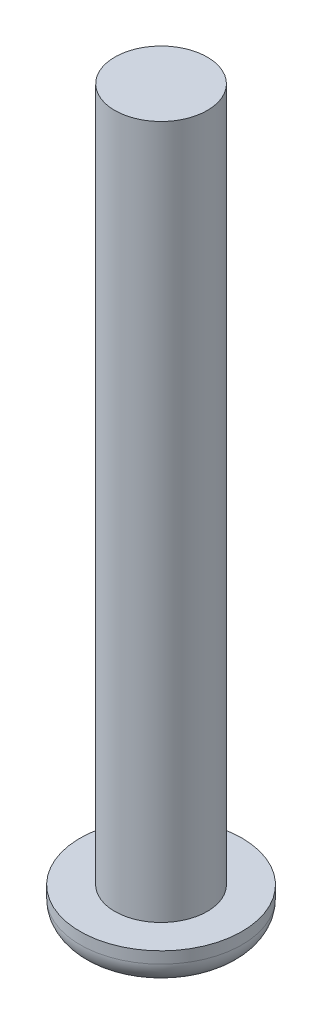
SolidWorks part; units mm, degrees
ref_plane "Front Plane" through (0, 0, 0) normal (0, 0, 1) x (1, 0, 0)
ref_plane "Top Plane" through (0, 0, 0) normal (0, 1, 0) x (1, 0, 0)
ref_plane "Right Plane" through (0, 0, 0) normal (1, 0, 0) x (0, 0, -1)
sketch "Sketch1" plane through (0, 0, 0) normal (0, 1, 0) x (1, 0, 0)
  circle A0 centre (0, 0) radius 4
  dimension "D1" = 8
extrude "Boss-Extrude1" add sketch "Sketch1" along normal blind 60 contours A0
sketch "Sketch2" plane through (0, 0, 0) normal (0, -1, 0) x (1, 0, 0)
  circle A0 centre (0, 0) radius 7
  circle A1 centre (0, 0) radius 4 construction
  circle A2 centre (0, 0) radius 4 construction
  dimension "D1" = 3
extrude "Boss-Extrude2" add sketch "Sketch2" along normal blind 3
fillet "Fillet1" radius 2 1 edges at (0, -3, -7)
sketch "Sketch3" plane through (0, -3, 0) normal (0, -1, 0) x (1, 0, 0)
  line L0 (0.375, 0.375) -> (1.5, 0.375)
  line L1 (-0.375, -1.5) -> (0.375, -1.5)
  line L2 (-0.375, -1.5) -> (-0.375, -0.375)
  line L3 (-0.375, 1.5) -> (0.375, 1.5)
  line L4 (0.375, -1.5) -> (0.375, -0.375)
  line L7 (-1.5, -0.375) -> (-0.375, -0.375)
  line L8 (-1.5, -0.375) -> (-1.5, 0.375)
  line L9 (-1.5, 0.375) -> (-0.375, 0.375)
  line L10 (1.5, -0.375) -> (1.5, 0.375)
  line L15 (0.375, 0.375) -> (0.375, 1.5)
  line L16 (0.375, -0.375) -> (1.5, -0.375)
  line L17 (-0.375, 0.375) -> (-0.375, 1.5)
  point P0 (0, 0)
  point P6 (0, 0)
  dimension "D1" = 3
  dimension "D2" = 0.75
extrude "Cut-Extrude1" cut sketch "Sketch3" against normal blind 1 draft 15
sketch "Sketch5" [suppressed] plane through (0, 0, 0) normal (0, 0, 1) x (1, 0, 0)
  line L0 (-3.5, -2) -> (3.5, -2) construction
  line L3 (0, 0) -> (0, 24) construction
  point P6 (0, 11)
  dimension "D1" = 13
  dimension "D2" = 26
sketch "Sketch6" plane through (0, 0, 0) normal (0, 0, 1) x (1, 0, 0)
  line L0 (0, 0) -> (0, 60) construction
  line L1 (4, 60) -> (-4, 60) construction
